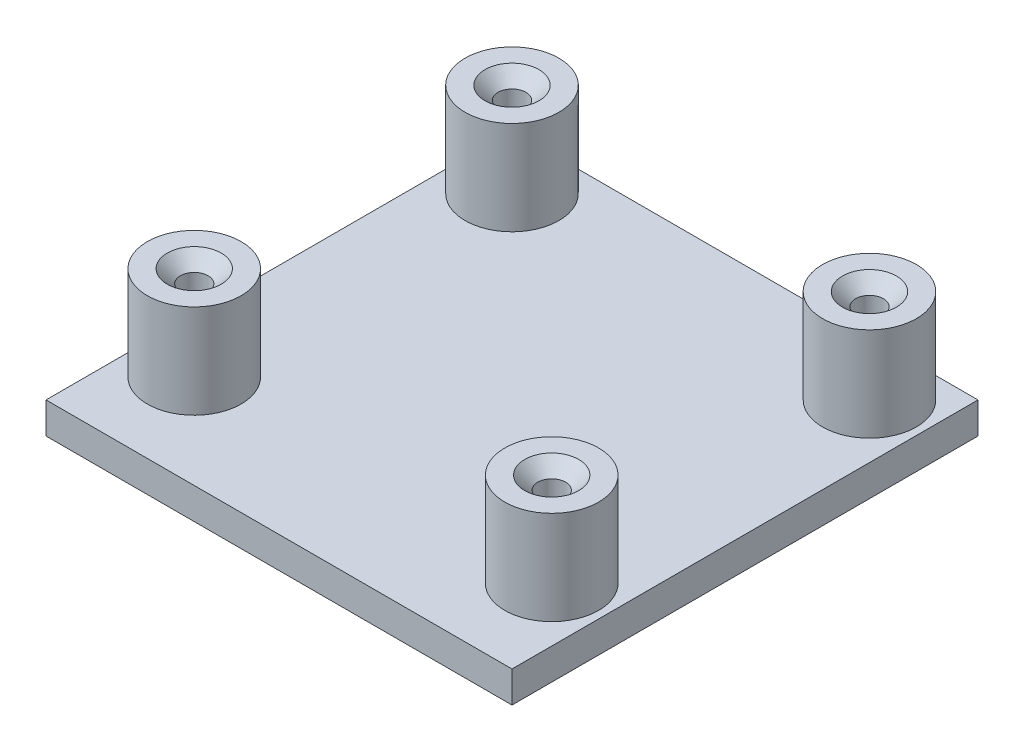
SolidWorks part; units mm, degrees
ref_plane "Front Plane" through (0, 0, 0) normal (0, 0, 1) x (1, 0, 0)
ref_plane "Top Plane" through (0, 0, 0) normal (0, 1, 0) x (1, 0, 0)
ref_plane "Right Plane" through (0, 0, 0) normal (1, 0, 0) x (0, 0, -1)
sketch "Sketch16" plane through (0, 0, 0) normal (0, 1, 0) x (1, 0, 0)
  line L1 (-14.9, -14.9) -> (14.9, -14.9)
  line L2 (-14.9, -14.9) -> (-14.9, 14.9)
  line L3 (-14.9, 14.9) -> (14.9, 14.9)
  line L4 (14.9, -14.9) -> (14.9, 14.9)
  line L5 (-14.9, -14.9) -> (14.9, 14.9) construction
  line L6 (-14.9, 14.9) -> (14.9, -14.9) construction
  point P0 (0, 0)
  dimension "D1" = 29.8
extrude "Boss-Extrude5" add sketch "Sketch16" along normal blind 2
ref_axis "Axis1" through (0, -10.1088, 0) along (0, 1, 0)
sketch "Sketch2" plane through (0, 0, 0) normal (0, 1, 0) x (1, 0, 0)
  line L1 (-15, -15) -> (15, -15)
  line L2 (-15, -15) -> (-15, 15)
  line L3 (-15, 15) -> (15, 15)
  line L4 (15, -15) -> (15, 15)
  line L5 (-15, -15) -> (15, 15) construction
  line L6 (-15, 15) -> (15, -15) construction
  point P0 (0, 0)
  dimension "D1" = 30
sketch "Sketch3" plane through (0, 0, 0) normal (0, 1, 0) x (1, 0, 0)
  line L0 (-14.43, 11.43) -> (-14.9, 11.43) construction
  line L1 (-11.43, -8.89) -> (11.43, -8.89) construction
  line L2 (-11.43, -8.89) -> (-11.43, 11.43) construction
  line L3 (-11.43, 11.43) -> (11.43, 11.43) construction
  line L4 (11.43, -8.89) -> (11.43, 11.43) construction
  line L5 (-11.43, -8.89) -> (11.43, 11.43) construction
  line L6 (-11.43, 11.43) -> (11.43, -8.89) construction
  line L7 (0, -8.89) -> (0, 0) construction
  line L8 (-14.9, 14.9) -> (-14.9, -14.9) construction
  line L9 (-11.43, 14.43) -> (-11.43, 14.9) construction
  line L10 (14.9, 14.9) -> (-14.9, 14.9) construction
  circle A0 centre (-11.43, 11.43) radius 3
  circle A1 centre (11.43, 11.43) radius 3
  circle A2 centre (11.43, -8.89) radius 3
  circle A3 centre (-11.43, -8.89) radius 3
  dimension "D2" = 6
  dimension "D1" = 22.86
  dimension "D3" = 20.32
extrude "Boss-Extrude2" add sketch "Sketch3" along normal offset from surface (8 mm away) 6 up to face at (0, 2, 0) offset beyond the face yes
hole_wizard "#2-56 Tapped Hole1" positions "3DSketch1" profile "Sketch15" tap size "#2-56" standard "ANSI Inch" end condition through all
sketch3d "3DSketch1"
  line L0 (-11.43, 8, -11.43) -> (-11.43, 2, -11.43) construction
  line L1 (11.43, 8, -11.43) -> (11.43, 2, -11.43) construction
  line L2 (-11.43, 8, 8.89) -> (-11.43, 2, 8.89) construction
  line L3 (11.43, 8, 8.89) -> (11.43, 2, 8.89) construction
  point P0 (-11.43, 8, -11.43)
  point P4 (11.43, 8, -11.43)
  point P8 (-11.43, 8, 8.89)
  point P12 (11.43, 8, 8.89)
sketch "Sketch15" plane through (-11.43, 8, -11.43) normal (1, 0, 0) x (0, 0, 1)
  line L0 (0, 0) -> (0, 8)
  line L1 (0, 8) -> (0.889, 8)
  line L2 (0.889, 8) -> (0.889, 0.8382)
  line L3 (0.889, 0.8382) -> (1.7272, 0)
  line L5 (1.7272, 0) -> (0, 0)
  line L6 (-0.889, 0.8382) -> (-1.7272, 0) construction
  line L11 (0, -6.35) -> (0, 107.95) construction
  dimension "Thru Tap Drill Dia." = 1.778
  dimension "Thru Tap Drill Depth" = 8
  dimension "Near C'Sink Dia." = 3.4544
  dimension "Near C'Sink Angle" = 90
